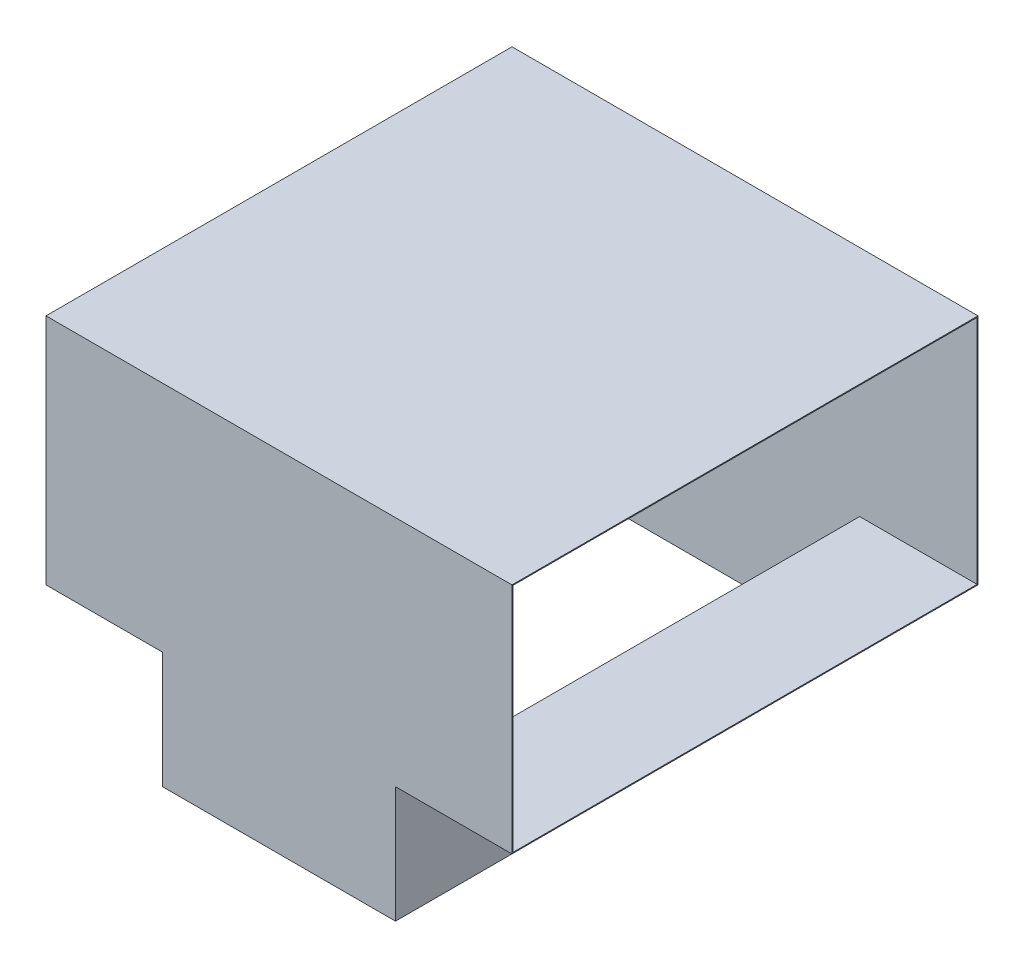
SolidWorks part; units mm, degrees
material "Plain Carbon Steel"
ref_plane "Front Plane" through (0, 0, 0) normal (0, 0, 1) x (1, 0, 0)
ref_plane "Top Plane" through (0, 0, 0) normal (0, 1, 0) x (1, 0, 0)
ref_plane "Right Plane" through (0, 0, 0) normal (1, 0, 0) x (0, 0, -1)
sketch "Sketch1" plane through (0, 0, 0) normal (1, 0, 0) x (0, 0, -1)
  line L0 (-500, 250) -> (500, -250) construction
  line L1 (-500, 250) -> (500, 250)
  line L2 (-500, 250) -> (-500, -250)
  line L3 (-500, -250) -> (500, -250)
  line L4 (500, 250) -> (500, -250)
  dimension "Width" = 1000
  dimension "Height" = 500
extrude "Extrude-Thin1" add sketch "Sketch1" along normal mid plane 1000 thin thin type one direction reverse wall 2
sketch "Sketch2" plane through (0, -250, 0) normal (0, -1, 0) x (1, 0, 0)
  line L1 (-250, 500) -> (250, 500)
  line L2 (-250, 500) -> (-250, -500)
  line L3 (-250, -500) -> (250, -500)
  line L4 (250, 500) -> (250, -500)
  line L6 (-250, 500) -> (250, -500) construction
  dimension "Height" = 500
  dimension "Width" = 1000
extrude "Extrude-Thin2" add sketch "Sketch2" along normal blind 250 thin thin type one direction reverse wall 2
sketch "Sketch3" plane through (0, -500, 0) normal (0, -1, 0) x (1, 0, 0)
  line L0 (-248, 498) -> (-248, -498) construction
  line L1 (248, 498) -> (-248, 498) construction
  line L2 (248, -498) -> (248, 498) construction
  line L3 (-248, -498) -> (248, -498) construction
  line L4 (-248, 498) -> (-248, -498)
  line L5 (248, 498) -> (-248, 498)
  line L6 (248, -498) -> (248, 498)
  line L7 (-248, -498) -> (248, -498)
extrude "Cut-Extrude1" cut sketch "Sketch3" against normal up to next
sketch "Sketch4" plane through (0, 0, 0) normal (0, 0, 1) x (1, 0, 0)
  line L0 (500, -248) -> (500, 248) construction
  line L1 (-500, -248) -> (-500, 248) construction
  line L2 (250, -500) -> (-250, -500) construction
  point P0 (500, 0)
  point P1 (0, 0)
  point P2 (-500, 0)
  point P4 (0, -500)
other "CPoint1"
ref_axis "Axis1" through (510, 0, 0) along (-1, 0, 0)
other "CPoint2"
ref_axis "Axis2" through (-510, 0, 0) along (1, 0, 0)
other "CPoint3"
ref_axis "Axis3" through (0, -510, 0) along (0, 1, 0)
other "RPoint1"
